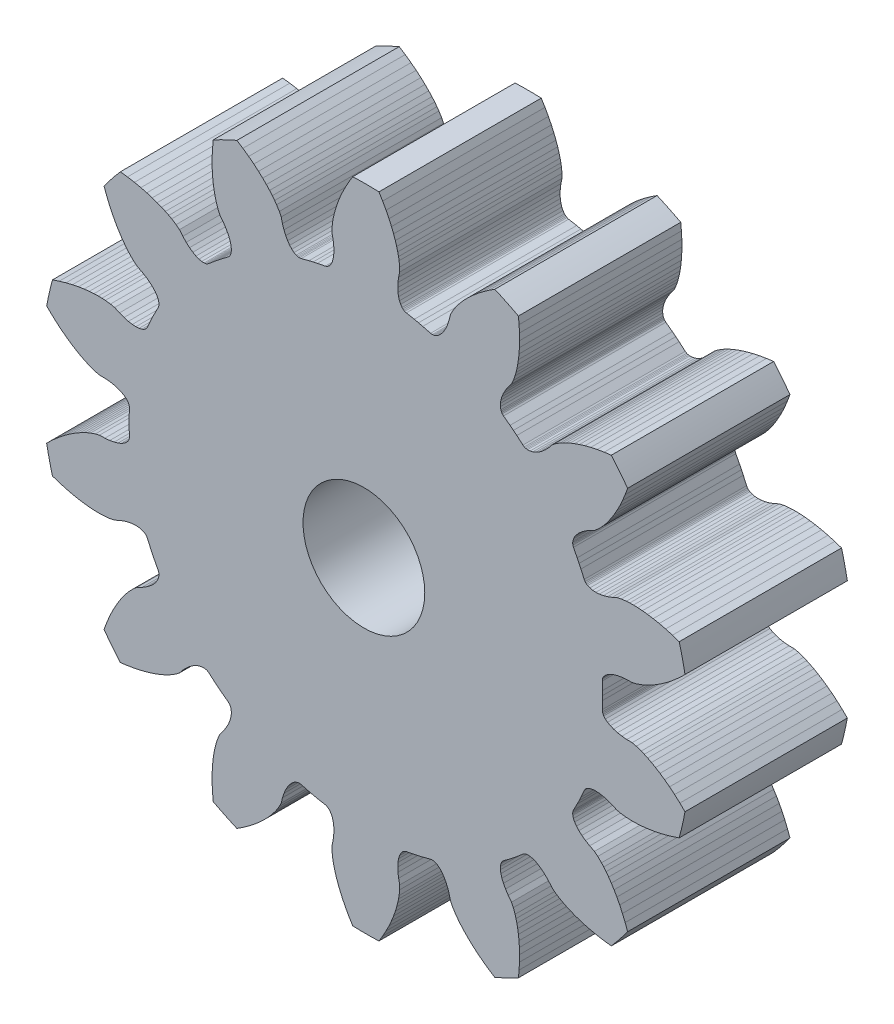
SolidWorks part; units mm, degrees
ref_plane "Front Plane" through (0, 0, 0) normal (0, 0, 1) x (1, 0, 0)
ref_plane "Top Plane" through (0, 0, 0) normal (0, 1, 0) x (1, 0, 0)
ref_plane "Right Plane" through (0, 0, 0) normal (1, 0, 0) x (0, 0, -1)
sketch "Model" plane through (0, 0, 0) normal (0, 0, 1) x (1, 0, 0)
  line L0 (0.9148, -6.8491) -> (1.0148, -6.6078)
  line L1 (1.0148, -6.6078) -> (1.1173, -6.3874)
  line L2 (1.1173, -6.3874) -> (1.2214, -6.1857)
  line L3 (1.2214, -6.1857) -> (1.3252, -6.004)
  line L4 (1.3252, -6.004) -> (1.4277, -5.8407)
  line L5 (1.4277, -5.8407) -> (1.5261, -5.6978)
  line L6 (1.5261, -5.6978) -> (1.6203, -5.5723)
  line L7 (1.6203, -5.5723) -> (1.708, -5.4652)
  line L8 (1.708, -5.4652) -> (1.7906, -5.3725)
  line L9 (1.7906, -5.3725) -> (1.9268, -5.2373)
  line L10 (1.9268, -5.2373) -> (2.0494, -5.137)
  line L11 (2.0494, -5.137) -> (2.2262, -5.0491)
  line L12 (2.2262, -5.0491) -> (2.3813, -4.9559)
  line L13 (2.3813, -4.9559) -> (2.5142, -4.8594)
  line L14 (2.5142, -4.8594) -> (2.6249, -4.7612)
  line L15 (2.6249, -4.7612) -> (2.7135, -4.663)
  line L16 (2.7135, -4.663) -> (2.7804, -4.5665)
  line L17 (2.7804, -4.5665) -> (2.8257, -4.4733)
  line L18 (2.8257, -4.4733) -> (2.8499, -4.385)
  line L19 (2.8499, -4.385) -> (2.8542, -4.3432)
  line L20 (2.8542, -4.3432) -> (2.8535, -4.3033)
  line L21 (2.8535, -4.3033) -> (2.8479, -4.2653)
  line L22 (2.8479, -4.2653) -> (2.8262, -4.2044)
  line L23 (2.8262, -4.2044) -> (2.6873, -3.9401)
  line L24 (2.6873, -3.9401) -> (2.6165, -3.7965)
  line L25 (2.6165, -3.7965) -> (2.5483, -3.6516)
  line L26 (2.5483, -3.6516) -> (2.4283, -3.3782)
  line L27 (2.4283, -3.3782) -> (2.3942, -3.3233)
  line L28 (2.3942, -3.3233) -> (2.3681, -3.2952)
  line L29 (2.3681, -3.2952) -> (2.3373, -3.2697)
  line L30 (2.3373, -3.2697) -> (2.3019, -3.2471)
  line L31 (2.3019, -3.2471) -> (2.2178, -3.211)
  line L32 (2.2178, -3.211) -> (2.1167, -3.1883)
  line L33 (2.1167, -3.1883) -> (1.9995, -3.1804)
  line L34 (1.9995, -3.1804) -> (1.8675, -3.1884)
  line L35 (1.8675, -3.1884) -> (1.7217, -3.2138)
  line L36 (1.7217, -3.2138) -> (1.5634, -3.2575)
  line L37 (1.5634, -3.2575) -> (1.3938, -3.3206)
  line L38 (1.3938, -3.3206) -> (1.2148, -3.4041)
  line L39 (1.2148, -3.4041) -> (1.06, -3.4374)
  line L40 (1.06, -3.4374) -> (0.8694, -3.4596)
  line L41 (0.8694, -3.4596) -> (0.7454, -3.4663)
  line L42 (0.7454, -3.4663) -> (0.607, -3.4681)
  line L43 (0.607, -3.4681) -> (0.4502, -3.4636)
  line L44 (0.4502, -3.4636) -> (0.2771, -3.4514)
  line L45 (0.2771, -3.4514) -> (0.0855, -3.4297)
  line L46 (0.0855, -3.4297) -> (-0.1213, -3.3975)
  line L47 (-0.1213, -3.3975) -> (-0.3439, -3.3532)
  line L48 (-0.3439, -3.3532) -> (-0.5801, -3.2959)
  line L49 (-0.5801, -3.2959) -> (-0.8311, -3.2237)
  line L50 (-0.8311, -3.2237) -> (-1.0818, -3.1401)
  line L51 (-1.2973, -2.1961) -> (-1.1076, -2.0119)
  line L52 (-1.1076, -2.0119) -> (-0.9129, -1.838)
  line L53 (-0.9129, -1.838) -> (-0.7249, -1.6838)
  line L54 (-0.7249, -1.6838) -> (-0.5436, -1.5473)
  line L55 (-0.5436, -1.5473) -> (-0.3713, -1.4286)
  line L56 (-0.3713, -1.4286) -> (-0.208, -1.326)
  line L57 (-0.208, -1.326) -> (-0.0574, -1.2399)
  line L58 (-0.0574, -1.2399) -> (0.0819, -1.1678)
  line L59 (0.0819, -1.1678) -> (0.2074, -1.1093)
  line L60 (0.2074, -1.1093) -> (0.3221, -1.0616)
  line L61 (0.3221, -1.0616) -> (0.5035, -0.9989)
  line L62 (0.5035, -0.9989) -> (0.6574, -0.9617)
  line L63 (0.6574, -0.9617) -> (0.8549, -0.9592)
  line L64 (0.8549, -0.9592) -> (1.035, -0.9426)
  line L65 (1.035, -0.9426) -> (1.1966, -0.9133)
  line L66 (1.1966, -0.9133) -> (1.339, -0.8728)
  line L67 (1.339, -0.8728) -> (1.4614, -0.8228)
  line L68 (1.4614, -0.8228) -> (1.5635, -0.7648)
  line L69 (1.5635, -0.7648) -> (1.6448, -0.7005)
  line L70 (1.6448, -0.7005) -> (1.7049, -0.6315)
  line L71 (1.7049, -0.6315) -> (1.727, -0.5957)
  line L72 (1.727, -0.5957) -> (1.7437, -0.5594)
  line L73 (1.7437, -0.5594) -> (1.755, -0.5228)
  line L74 (1.755, -0.5228) -> (1.7619, -0.4585)
  line L75 (1.7619, -0.4585) -> (1.7514, -0.1601)
  line L76 (1.7514, -0.1601) -> (1.75, 0)
  line L77 (1.75, 0) -> (1.7514, 0.1601)
  line L78 (1.7514, 0.1601) -> (1.7619, 0.4585)
  line L79 (1.7619, 0.4585) -> (1.755, 0.5228)
  line L80 (1.755, 0.5228) -> (1.7437, 0.5594)
  line L81 (1.7437, 0.5594) -> (1.727, 0.5957)
  line L82 (1.727, 0.5957) -> (1.7049, 0.6315)
  line L83 (1.7049, 0.6315) -> (1.6448, 0.7005)
  line L84 (1.6448, 0.7005) -> (1.5635, 0.7648)
  line L85 (1.5635, 0.7648) -> (1.4614, 0.8228)
  line L86 (1.4614, 0.8228) -> (1.339, 0.8728)
  line L87 (1.339, 0.8728) -> (1.1966, 0.9133)
  line L88 (1.1966, 0.9133) -> (1.035, 0.9426)
  line L89 (1.035, 0.9426) -> (0.8549, 0.9592)
  line L90 (0.8549, 0.9592) -> (0.6574, 0.9617)
  line L91 (0.6574, 0.9617) -> (0.5035, 0.9989)
  line L92 (0.5035, 0.9989) -> (0.3221, 1.0616)
  line L93 (0.3221, 1.0616) -> (0.2074, 1.1093)
  line L94 (0.2074, 1.1093) -> (0.0819, 1.1678)
  line L95 (0.0819, 1.1678) -> (-0.0574, 1.2399)
  line L96 (-0.0574, 1.2399) -> (-0.208, 1.326)
  line L97 (-0.208, 1.326) -> (-0.3713, 1.4286)
  line L98 (-0.3713, 1.4286) -> (-0.5436, 1.5473)
  line L99 (-0.5436, 1.5473) -> (-0.7249, 1.6838)
  line L100 (-0.7249, 1.6838) -> (-0.9129, 1.838)
  line L101 (-0.9129, 1.838) -> (-1.1076, 2.0119)
  line L102 (-1.1076, 2.0119) -> (-1.2973, 2.1961)
  line L103 (-1.0818, 3.1401) -> (-0.8311, 3.2237)
  line L104 (-0.8311, 3.2237) -> (-0.5801, 3.2959)
  line L105 (-0.5801, 3.2959) -> (-0.3439, 3.3532)
  line L106 (-0.3439, 3.3532) -> (-0.1213, 3.3975)
  line L107 (-0.1213, 3.3975) -> (0.0855, 3.4297)
  line L108 (0.0855, 3.4297) -> (0.2771, 3.4514)
  line L109 (0.2771, 3.4514) -> (0.4502, 3.4636)
  line L110 (0.4502, 3.4636) -> (0.607, 3.4681)
  line L111 (0.607, 3.4681) -> (0.7454, 3.4663)
  line L112 (0.7454, 3.4663) -> (0.8694, 3.4596)
  line L113 (0.8694, 3.4596) -> (1.06, 3.4374)
  line L114 (1.06, 3.4374) -> (1.2148, 3.4041)
  line L115 (1.2148, 3.4041) -> (1.3938, 3.3206)
  line L116 (1.3938, 3.3206) -> (1.5634, 3.2575)
  line L117 (1.5634, 3.2575) -> (1.7217, 3.2138)
  line L118 (1.7217, 3.2138) -> (1.8675, 3.1884)
  line L119 (1.8675, 3.1884) -> (1.9995, 3.1804)
  line L120 (1.9995, 3.1804) -> (2.1167, 3.1883)
  line L121 (2.1167, 3.1883) -> (2.2178, 3.211)
  line L122 (2.2178, 3.211) -> (2.3019, 3.2471)
  line L123 (2.3019, 3.2471) -> (2.3373, 3.2697)
  line L124 (2.3373, 3.2697) -> (2.3681, 3.2952)
  line L125 (2.3681, 3.2952) -> (2.3942, 3.3233)
  line L126 (2.3942, 3.3233) -> (2.4283, 3.3782)
  line L127 (2.4283, 3.3782) -> (2.5483, 3.6516)
  line L128 (2.5483, 3.6516) -> (2.6165, 3.7965)
  line L129 (2.6165, 3.7965) -> (2.6873, 3.9401)
  line L130 (2.6873, 3.9401) -> (2.8262, 4.2044)
  line L131 (2.8262, 4.2044) -> (2.8479, 4.2653)
  line L132 (2.8479, 4.2653) -> (2.8535, 4.3033)
  line L133 (2.8535, 4.3033) -> (2.8542, 4.3432)
  line L134 (2.8542, 4.3432) -> (2.8499, 4.385)
  line L135 (2.8499, 4.385) -> (2.8257, 4.4733)
  line L136 (2.8257, 4.4733) -> (2.7804, 4.5665)
  line L137 (2.7804, 4.5665) -> (2.7135, 4.663)
  line L138 (2.7135, 4.663) -> (2.6249, 4.7612)
  line L139 (2.6249, 4.7612) -> (2.5142, 4.8594)
  line L140 (2.5142, 4.8594) -> (2.3813, 4.9559)
  line L141 (2.3813, 4.9559) -> (2.2262, 5.0491)
  line L142 (2.2262, 5.0491) -> (2.0494, 5.137)
  line L143 (2.0494, 5.137) -> (1.9268, 5.2373)
  line L144 (1.9268, 5.2373) -> (1.7906, 5.3725)
  line L145 (1.7906, 5.3725) -> (1.708, 5.4652)
  line L146 (1.708, 5.4652) -> (1.6203, 5.5723)
  line L147 (1.6203, 5.5723) -> (1.5261, 5.6978)
  line L148 (1.5261, 5.6978) -> (1.4277, 5.8407)
  line L149 (1.4277, 5.8407) -> (1.3252, 6.004)
  line L150 (1.3252, 6.004) -> (1.2214, 6.1857)
  line L151 (1.2214, 6.1857) -> (1.1173, 6.3874)
  line L152 (1.1173, 6.3874) -> (1.0148, 6.6078)
  line L153 (1.0148, 6.6078) -> (0.9148, 6.8491)
  line L154 (0.9148, 6.8491) -> (0.8238, 7.0973)
  line L155 (1.4275, 7.8543) -> (1.6898, 7.8208)
  line L156 (1.6898, 7.8208) -> (1.9472, 7.777)
  line L157 (1.9472, 7.777) -> (2.1849, 7.7262)
  line L158 (2.1849, 7.7262) -> (2.4047, 7.6695)
  line L159 (2.4047, 7.6695) -> (2.6049, 7.6088)
  line L160 (2.6049, 7.6088) -> (2.7869, 7.5451)
  line L161 (2.7869, 7.5451) -> (2.9482, 7.4811)
  line L162 (2.9482, 7.4811) -> (3.0914, 7.4171)
  line L163 (3.0914, 7.4171) -> (3.2154, 7.3554)
  line L164 (3.2154, 7.3554) -> (3.3242, 7.2955)
  line L165 (3.3242, 7.2955) -> (3.4863, 7.1928)
  line L166 (3.4863, 7.1928) -> (3.6113, 7.0957)
  line L167 (3.6113, 7.0957) -> (3.7364, 6.9428)
  line L168 (3.7364, 6.9428) -> (3.8617, 6.8123)
  line L169 (3.8617, 6.8123) -> (3.9854, 6.7043)
  line L170 (3.9854, 6.7043) -> (4.1058, 6.6182)
  line L171 (4.1058, 6.6182) -> (4.2213, 6.5536)
  line L172 (4.2213, 6.5536) -> (4.3302, 6.51)
  line L173 (4.3302, 6.51) -> (4.4312, 6.4865)
  line L174 (4.4312, 6.4865) -> (4.5226, 6.4826)
  line L175 (4.5226, 6.4826) -> (4.5643, 6.4876)
  line L176 (4.5643, 6.4876) -> (4.6031, 6.4972)
  line L177 (4.6031, 6.4972) -> (4.6388, 6.5112)
  line L178 (4.6388, 6.5112) -> (4.6934, 6.5459)
  line L179 (4.6934, 6.5459) -> (4.9202, 6.7401)
  line L180 (4.9202, 6.7401) -> (5.0445, 6.841)
  line L181 (5.0445, 6.841) -> (5.1706, 6.9397)
  line L182 (5.1706, 6.9397) -> (5.4103, 7.1176)
  line L183 (5.4103, 7.1176) -> (5.4563, 7.1631)
  line L184 (5.4563, 7.1631) -> (5.4779, 7.1948)
  line L185 (5.4779, 7.1948) -> (5.4959, 7.2305)
  line L186 (5.4959, 7.2305) -> (5.5101, 7.27)
  line L187 (5.5101, 7.27) -> (5.5265, 7.3601)
  line L188 (5.5265, 7.3601) -> (5.5262, 7.4637)
  line L189 (5.5262, 7.4637) -> (5.5078, 7.5796)
  line L190 (5.5078, 7.5796) -> (5.4706, 7.7066)
  line L191 (5.4706, 7.7066) -> (5.4135, 7.8431)
  line L192 (5.4135, 7.8431) -> (5.3356, 7.9877)
  line L193 (5.3356, 7.9877) -> (5.2363, 8.1389)
  line L194 (5.2363, 8.1389) -> (5.1151, 8.2949)
  line L195 (5.1151, 8.2949) -> (5.0482, 8.4384)
  line L196 (5.0482, 8.4384) -> (4.9842, 8.6193)
  line L197 (4.9842, 8.6193) -> (4.95, 8.7387)
  line L198 (4.95, 8.7387) -> (4.9174, 8.8733)
  line L199 (4.9174, 8.8733) -> (4.8869, 9.0271)
  line L200 (4.8869, 9.0271) -> (4.8603, 9.1986)
  line L201 (4.8603, 9.1986) -> (4.8388, 9.3902)
  line L202 (4.8388, 9.3902) -> (4.8242, 9.599)
  line L203 (4.8242, 9.599) -> (4.8178, 9.8259)
  line L204 (4.8178, 9.8259) -> (4.8212, 10.0689)
  line L205 (4.8212, 10.0689) -> (4.8357, 10.3296)
  line L206 (4.8357, 10.3296) -> (4.8615, 10.5927)
  line L207 (5.7338, 11.0128) -> (5.9556, 10.8689)
  line L208 (5.9556, 10.8689) -> (6.1685, 10.7177)
  line L209 (6.1685, 10.7177) -> (6.3606, 10.5688)
  line L210 (6.3606, 10.5688) -> (6.534, 10.4224)
  line L211 (6.534, 10.4224) -> (6.6881, 10.2808)
  line L212 (6.6881, 10.2808) -> (6.8245, 10.1445)
  line L213 (6.8245, 10.1445) -> (6.942, 10.0168)
  line L214 (6.942, 10.0168) -> (7.0433, 9.897)
  line L215 (7.0433, 9.897) -> (7.1282, 9.7877)
  line L216 (7.1282, 9.7877) -> (7.2002, 9.6865)
  line L217 (7.2002, 9.6865) -> (7.3017, 9.5236)
  line L218 (7.3017, 9.5236) -> (7.3722, 9.3819)
  line L219 (7.3722, 9.3819) -> (7.4186, 9.1899)
  line L220 (7.4186, 9.1899) -> (7.4749, 9.0179)
  line L221 (7.4749, 9.0179) -> (7.5394, 8.8669)
  line L222 (7.5394, 8.8669) -> (7.6105, 8.7371)
  line L223 (7.6105, 8.7371) -> (7.6866, 8.6289)
  line L224 (7.6866, 8.6289) -> (7.7658, 8.5422)
  line L225 (7.7658, 8.5422) -> (7.8466, 8.4773)
  line L226 (7.8466, 8.4773) -> (7.9272, 8.4341)
  line L227 (7.9272, 8.4341) -> (7.967, 8.4205)
  line L228 (7.967, 8.4205) -> (8.0061, 8.4123)
  line L229 (8.0061, 8.4123) -> (8.0444, 8.4094)
  line L230 (8.0444, 8.4094) -> (8.1086, 8.417)
  line L231 (8.1086, 8.417) -> (8.3971, 8.4936)
  line L232 (8.3971, 8.4936) -> (8.5529, 8.5306)
  line L233 (8.5529, 8.5306) -> (8.7094, 8.5648)
  line L234 (8.7094, 8.5648) -> (9.0026, 8.621)
  line L235 (9.0026, 8.621) -> (9.0637, 8.6421)
  line L236 (9.0637, 8.6421) -> (9.0969, 8.6613)
  line L237 (9.0969, 8.6613) -> (9.1286, 8.6856)
  line L238 (9.1286, 8.6856) -> (9.1586, 8.7151)
  line L239 (9.1586, 8.7151) -> (9.2125, 8.7891)
  line L240 (9.2125, 8.7891) -> (9.2571, 8.8826)
  line L241 (9.2571, 8.8826) -> (9.2909, 8.995)
  line L242 (9.2909, 8.995) -> (9.3124, 9.1256)
  line L243 (9.3124, 9.1256) -> (9.3202, 9.2733)
  line L244 (9.3202, 9.2733) -> (9.3128, 9.4374)
  line L245 (9.3128, 9.4374) -> (9.2889, 9.6168)
  line L246 (9.2889, 9.6168) -> (9.2474, 9.8099)
  line L247 (9.2474, 9.8099) -> (9.2494, 9.9682)
  line L248 (9.2494, 9.9682) -> (9.2702, 10.159)
  line L249 (9.2702, 10.159) -> (9.2912, 10.2814)
  line L250 (9.2912, 10.2814) -> (9.3202, 10.4167)
  line L251 (9.3202, 10.4167) -> (9.3595, 10.5686)
  line L252 (9.3595, 10.5686) -> (9.41, 10.7346)
  line L253 (9.41, 10.7346) -> (9.4737, 10.9166)
  line L254 (9.4737, 10.9166) -> (9.5511, 11.111)
  line L255 (9.5511, 11.111) -> (9.6438, 11.3182)
  line L256 (9.6438, 11.3182) -> (9.7523, 11.5357)
  line L257 (9.7523, 11.5357) -> (9.8785, 11.7643)
  line L258 (9.8785, 11.7643) -> (10.0159, 11.9902)
  line L259 (10.9841, 11.9902) -> (11.1215, 11.7643)
  line L260 (11.1215, 11.7643) -> (11.2477, 11.5357)
  line L261 (11.2477, 11.5357) -> (11.3562, 11.3182)
  line L262 (11.3562, 11.3182) -> (11.4489, 11.111)
  line L263 (11.4489, 11.111) -> (11.5263, 10.9166)
  line L264 (11.5263, 10.9166) -> (11.59, 10.7346)
  line L265 (11.59, 10.7346) -> (11.6405, 10.5686)
  line L266 (11.6405, 10.5686) -> (11.6798, 10.4167)
  line L267 (11.6798, 10.4167) -> (11.7088, 10.2814)
  line L268 (11.7088, 10.2814) -> (11.7298, 10.159)
  line L269 (11.7298, 10.159) -> (11.7506, 9.9682)
  line L270 (11.7506, 9.9682) -> (11.7526, 9.8099)
  line L271 (11.7526, 9.8099) -> (11.7111, 9.6168)
  line L272 (11.7111, 9.6168) -> (11.6872, 9.4374)
  line L273 (11.6872, 9.4374) -> (11.6798, 9.2733)
  line L274 (11.6798, 9.2733) -> (11.6876, 9.1256)
  line L275 (11.6876, 9.1256) -> (11.7091, 8.995)
  line L276 (11.7091, 8.995) -> (11.7429, 8.8826)
  line L277 (11.7429, 8.8826) -> (11.7875, 8.7891)
  line L278 (11.7875, 8.7891) -> (11.8414, 8.7151)
  line L279 (11.8414, 8.7151) -> (11.8714, 8.6856)
  line L280 (11.8714, 8.6856) -> (11.9031, 8.6613)
  line L281 (11.9031, 8.6613) -> (11.9363, 8.6421)
  line L282 (11.9363, 8.6421) -> (11.9974, 8.621)
  line L283 (11.9974, 8.621) -> (12.2906, 8.5648)
  line L284 (12.2906, 8.5648) -> (12.4471, 8.5306)
  line L285 (12.4471, 8.5306) -> (12.6029, 8.4936)
  line L286 (12.6029, 8.4936) -> (12.8914, 8.417)
  line L287 (12.8914, 8.417) -> (12.9556, 8.4094)
  line L288 (12.9556, 8.4094) -> (12.9939, 8.4123)
  line L289 (12.9939, 8.4123) -> (13.033, 8.4205)
  line L290 (13.033, 8.4205) -> (13.0728, 8.4341)
  line L291 (13.0728, 8.4341) -> (13.1534, 8.4773)
  line L292 (13.1534, 8.4773) -> (13.2342, 8.5422)
  line L293 (13.2342, 8.5422) -> (13.3134, 8.6289)
  line L294 (13.3134, 8.6289) -> (13.3895, 8.7371)
  line L295 (13.3895, 8.7371) -> (13.4606, 8.8669)
  line L296 (13.4606, 8.8669) -> (13.5251, 9.0179)
  line L297 (13.5251, 9.0179) -> (13.5814, 9.1899)
  line L298 (13.5814, 9.1899) -> (13.6278, 9.3819)
  line L299 (13.6278, 9.3819) -> (13.6983, 9.5236)
  line L300 (13.6983, 9.5236) -> (13.7998, 9.6865)
  line L301 (13.7998, 9.6865) -> (13.8718, 9.7877)
  line L302 (13.8718, 9.7877) -> (13.9567, 9.897)
  line L303 (13.9567, 9.897) -> (14.058, 10.0168)
  line L304 (14.058, 10.0168) -> (14.1755, 10.1445)
  line L305 (14.1755, 10.1445) -> (14.3119, 10.2808)
  line L306 (14.3119, 10.2808) -> (14.466, 10.4224)
  line L307 (14.466, 10.4224) -> (14.6394, 10.5688)
  line L308 (14.6394, 10.5688) -> (14.8315, 10.7177)
  line L309 (14.8315, 10.7177) -> (15.0444, 10.8689)
  line L310 (15.0444, 10.8689) -> (15.2662, 11.0128)
  line L311 (16.1385, 10.5927) -> (16.1643, 10.3296)
  line L312 (16.1643, 10.3296) -> (16.1788, 10.0689)
  line L313 (16.1788, 10.0689) -> (16.1822, 9.8259)
  line L314 (16.1822, 9.8259) -> (16.1758, 9.599)
  line L315 (16.1758, 9.599) -> (16.1612, 9.3902)
  line L316 (16.1612, 9.3902) -> (16.1397, 9.1986)
  line L317 (16.1397, 9.1986) -> (16.1131, 9.0271)
  line L318 (16.1131, 9.0271) -> (16.0826, 8.8733)
  line L319 (16.0826, 8.8733) -> (16.05, 8.7387)
  line L320 (16.05, 8.7387) -> (16.0158, 8.6193)
  line L321 (16.0158, 8.6193) -> (15.9518, 8.4384)
  line L322 (15.9518, 8.4384) -> (15.8849, 8.2949)
  line L323 (15.8849, 8.2949) -> (15.7637, 8.1389)
  line L324 (15.7637, 8.1389) -> (15.6644, 7.9877)
  line L325 (15.6644, 7.9877) -> (15.5865, 7.8431)
  line L326 (15.5865, 7.8431) -> (15.5294, 7.7066)
  line L327 (15.5294, 7.7066) -> (15.4922, 7.5796)
  line L328 (15.4922, 7.5796) -> (15.4738, 7.4637)
  line L329 (15.4738, 7.4637) -> (15.4735, 7.3601)
  line L330 (15.4735, 7.3601) -> (15.4899, 7.27)
  line L331 (15.4899, 7.27) -> (15.5041, 7.2305)
  line L332 (15.5041, 7.2305) -> (15.5221, 7.1948)
  line L333 (15.5221, 7.1948) -> (15.5437, 7.1631)
  line L334 (15.5437, 7.1631) -> (15.5897, 7.1176)
  line L335 (15.5897, 7.1176) -> (15.8294, 6.9397)
  line L336 (15.8294, 6.9397) -> (15.9555, 6.841)
  line L337 (15.9555, 6.841) -> (16.0798, 6.7401)
  line L338 (16.0798, 6.7401) -> (16.3066, 6.5459)
  line L339 (16.3066, 6.5459) -> (16.3612, 6.5112)
  line L340 (16.3612, 6.5112) -> (16.3969, 6.4972)
  line L341 (16.3969, 6.4972) -> (16.4357, 6.4876)
  line L342 (16.4357, 6.4876) -> (16.4774, 6.4826)
  line L343 (16.4774, 6.4826) -> (16.5688, 6.4865)
  line L344 (16.5688, 6.4865) -> (16.6698, 6.51)
  line L345 (16.6698, 6.51) -> (16.7787, 6.5536)
  line L346 (16.7787, 6.5536) -> (16.8942, 6.6182)
  line L347 (16.8942, 6.6182) -> (17.0146, 6.7043)
  line L348 (17.0146, 6.7043) -> (17.1383, 6.8123)
  line L349 (17.1383, 6.8123) -> (17.2636, 6.9428)
  line L350 (17.2636, 6.9428) -> (17.3887, 7.0957)
  line L351 (17.3887, 7.0957) -> (17.5137, 7.1928)
  line L352 (17.5137, 7.1928) -> (17.6758, 7.2955)
  line L353 (17.6758, 7.2955) -> (17.7846, 7.3554)
  line L354 (17.7846, 7.3554) -> (17.9086, 7.4171)
  line L355 (17.9086, 7.4171) -> (18.0518, 7.4811)
  line L356 (18.0518, 7.4811) -> (18.2131, 7.5451)
  line L357 (18.2131, 7.5451) -> (18.3951, 7.6088)
  line L358 (18.3951, 7.6088) -> (18.5953, 7.6695)
  line L359 (18.5953, 7.6695) -> (18.8151, 7.7262)
  line L360 (18.8151, 7.7262) -> (19.0528, 7.777)
  line L361 (19.0528, 7.777) -> (19.3102, 7.8208)
  line L362 (19.3102, 7.8208) -> (19.5725, 7.8543)
  line L363 (20.1762, 7.0973) -> (20.0852, 6.8491)
  line L364 (20.0852, 6.8491) -> (19.9852, 6.6078)
  line L365 (19.9852, 6.6078) -> (19.8827, 6.3874)
  line L366 (19.8827, 6.3874) -> (19.7786, 6.1857)
  line L367 (19.7786, 6.1857) -> (19.6748, 6.004)
  line L368 (19.6748, 6.004) -> (19.5723, 5.8407)
  line L369 (19.5723, 5.8407) -> (19.4739, 5.6978)
  line L370 (19.4739, 5.6978) -> (19.3797, 5.5723)
  line L371 (19.3797, 5.5723) -> (19.292, 5.4652)
  line L372 (19.292, 5.4652) -> (19.2094, 5.3725)
  line L373 (19.2094, 5.3725) -> (19.0732, 5.2373)
  line L374 (19.0732, 5.2373) -> (18.9506, 5.137)
  line L375 (18.9506, 5.137) -> (18.7738, 5.0491)
  line L376 (18.7738, 5.0491) -> (18.6187, 4.9559)
  line L377 (18.6187, 4.9559) -> (18.4858, 4.8594)
  line L378 (18.4858, 4.8594) -> (18.3751, 4.7612)
  line L379 (18.3751, 4.7612) -> (18.2865, 4.663)
  line L380 (18.2865, 4.663) -> (18.2196, 4.5665)
  line L381 (18.2196, 4.5665) -> (18.1743, 4.4733)
  line L382 (18.1743, 4.4733) -> (18.1501, 4.385)
  line L383 (18.1501, 4.385) -> (18.1458, 4.3432)
  line L384 (18.1458, 4.3432) -> (18.1465, 4.3033)
  line L385 (18.1465, 4.3033) -> (18.1521, 4.2653)
  line L386 (18.1521, 4.2653) -> (18.1738, 4.2044)
  line L387 (18.1738, 4.2044) -> (18.3127, 3.9401)
  line L388 (18.3127, 3.9401) -> (18.3835, 3.7965)
  line L389 (18.3835, 3.7965) -> (18.4517, 3.6516)
  line L390 (18.4517, 3.6516) -> (18.5717, 3.3782)
  line L391 (18.5717, 3.3782) -> (18.6058, 3.3233)
  line L392 (18.6058, 3.3233) -> (18.6319, 3.2952)
  line L393 (18.6319, 3.2952) -> (18.6627, 3.2697)
  line L394 (18.6627, 3.2697) -> (18.6981, 3.2471)
  line L395 (18.6981, 3.2471) -> (18.7822, 3.211)
  line L396 (18.7822, 3.211) -> (18.8833, 3.1883)
  line L397 (18.8833, 3.1883) -> (19.0005, 3.1804)
  line L398 (19.0005, 3.1804) -> (19.1325, 3.1884)
  line L399 (19.1325, 3.1884) -> (19.2783, 3.2138)
  line L400 (19.2783, 3.2138) -> (19.4366, 3.2575)
  line L401 (19.4366, 3.2575) -> (19.6062, 3.3206)
  line L402 (19.6062, 3.3206) -> (19.7852, 3.4041)
  line L403 (19.7852, 3.4041) -> (19.94, 3.4374)
  line L404 (19.94, 3.4374) -> (20.1306, 3.4596)
  line L405 (20.1306, 3.4596) -> (20.2546, 3.4663)
  line L406 (20.2546, 3.4663) -> (20.393, 3.4681)
  line L407 (20.393, 3.4681) -> (20.5498, 3.4636)
  line L408 (20.5498, 3.4636) -> (20.7229, 3.4514)
  line L409 (20.7229, 3.4514) -> (20.9145, 3.4297)
  line L410 (20.9145, 3.4297) -> (21.1213, 3.3975)
  line L411 (21.1213, 3.3975) -> (21.3439, 3.3532)
  line L412 (21.3439, 3.3532) -> (21.5801, 3.2959)
  line L413 (21.5801, 3.2959) -> (21.8311, 3.2237)
  line L414 (21.8311, 3.2237) -> (22.0818, 3.1401)
  line L415 (22.2973, 2.1961) -> (22.1076, 2.0119)
  line L416 (22.1076, 2.0119) -> (21.9129, 1.838)
  line L417 (21.9129, 1.838) -> (21.7249, 1.6838)
  line L418 (21.7249, 1.6838) -> (21.5436, 1.5473)
  line L419 (21.5436, 1.5473) -> (21.3713, 1.4286)
  line L420 (21.3713, 1.4286) -> (21.208, 1.326)
  line L421 (21.208, 1.326) -> (21.0574, 1.2399)
  line L422 (21.0574, 1.2399) -> (20.9181, 1.1678)
  line L423 (20.9181, 1.1678) -> (20.7926, 1.1093)
  line L424 (20.7926, 1.1093) -> (20.6779, 1.0616)
  line L425 (20.6779, 1.0616) -> (20.4965, 0.9989)
  line L426 (20.4965, 0.9989) -> (20.3426, 0.9617)
  line L427 (20.3426, 0.9617) -> (20.1451, 0.9592)
  line L428 (20.1451, 0.9592) -> (19.965, 0.9426)
  line L429 (19.965, 0.9426) -> (19.8034, 0.9133)
  line L430 (19.8034, 0.9133) -> (19.661, 0.8728)
  line L431 (19.661, 0.8728) -> (19.5386, 0.8228)
  line L432 (19.5386, 0.8228) -> (19.4365, 0.7648)
  line L433 (19.4365, 0.7648) -> (19.3552, 0.7005)
  line L434 (19.3552, 0.7005) -> (19.2951, 0.6315)
  line L435 (19.2951, 0.6315) -> (19.273, 0.5957)
  line L436 (19.273, 0.5957) -> (19.2563, 0.5594)
  line L437 (19.2563, 0.5594) -> (19.245, 0.5228)
  line L438 (19.245, 0.5228) -> (19.2381, 0.4585)
  line L439 (19.2381, 0.4585) -> (19.2486, 0.1601)
  line L440 (19.2486, 0.1601) -> (19.25, 0)
  line L441 (19.25, 0) -> (19.2486, -0.1601)
  line L442 (19.2486, -0.1601) -> (19.2381, -0.4585)
  line L443 (19.2381, -0.4585) -> (19.245, -0.5228)
  line L444 (19.245, -0.5228) -> (19.2563, -0.5594)
  line L445 (19.2563, -0.5594) -> (19.273, -0.5957)
  line L446 (19.273, -0.5957) -> (19.2951, -0.6315)
  line L447 (19.2951, -0.6315) -> (19.3552, -0.7005)
  line L448 (19.3552, -0.7005) -> (19.4365, -0.7648)
  line L449 (19.4365, -0.7648) -> (19.5386, -0.8228)
  line L450 (19.5386, -0.8228) -> (19.661, -0.8728)
  line L451 (19.661, -0.8728) -> (19.8034, -0.9133)
  line L452 (19.8034, -0.9133) -> (19.965, -0.9426)
  line L453 (19.965, -0.9426) -> (20.1451, -0.9592)
  line L454 (20.1451, -0.9592) -> (20.3426, -0.9617)
  line L455 (20.3426, -0.9617) -> (20.4965, -0.9989)
  line L456 (20.4965, -0.9989) -> (20.6779, -1.0616)
  line L457 (20.6779, -1.0616) -> (20.7926, -1.1093)
  line L458 (20.7926, -1.1093) -> (20.9181, -1.1678)
  line L459 (20.9181, -1.1678) -> (21.0574, -1.2399)
  line L460 (21.0574, -1.2399) -> (21.208, -1.326)
  line L461 (21.208, -1.326) -> (21.3713, -1.4286)
  line L462 (21.3713, -1.4286) -> (21.5436, -1.5473)
  line L463 (21.5436, -1.5473) -> (21.7249, -1.6838)
  line L464 (21.7249, -1.6838) -> (21.9129, -1.838)
  line L465 (21.9129, -1.838) -> (22.1076, -2.0119)
  line L466 (22.1076, -2.0119) -> (22.2973, -2.1961)
  line L467 (22.0818, -3.1401) -> (21.8311, -3.2237)
  line L468 (21.8311, -3.2237) -> (21.5801, -3.2959)
  line L469 (21.5801, -3.2959) -> (21.3439, -3.3532)
  line L470 (21.3439, -3.3532) -> (21.1213, -3.3975)
  line L471 (21.1213, -3.3975) -> (20.9145, -3.4297)
  line L472 (20.9145, -3.4297) -> (20.7229, -3.4514)
  line L473 (20.7229, -3.4514) -> (20.5498, -3.4636)
  line L474 (20.5498, -3.4636) -> (20.393, -3.4681)
  line L475 (20.393, -3.4681) -> (20.2546, -3.4663)
  line L476 (20.2546, -3.4663) -> (20.1306, -3.4596)
  line L477 (20.1306, -3.4596) -> (19.94, -3.4374)
  line L478 (19.94, -3.4374) -> (19.7852, -3.4041)
  line L479 (19.7852, -3.4041) -> (19.6062, -3.3206)
  line L480 (19.6062, -3.3206) -> (19.4366, -3.2575)
  line L481 (19.4366, -3.2575) -> (19.2783, -3.2138)
  line L482 (19.2783, -3.2138) -> (19.1325, -3.1884)
  line L483 (19.1325, -3.1884) -> (19.0005, -3.1804)
  line L484 (19.0005, -3.1804) -> (18.8833, -3.1883)
  line L485 (18.8833, -3.1883) -> (18.7822, -3.211)
  line L486 (18.7822, -3.211) -> (18.6981, -3.2471)
  line L487 (18.6981, -3.2471) -> (18.6627, -3.2697)
  line L488 (18.6627, -3.2697) -> (18.6319, -3.2952)
  line L489 (18.6319, -3.2952) -> (18.6058, -3.3233)
  line L490 (18.6058, -3.3233) -> (18.5717, -3.3782)
  line L491 (18.5717, -3.3782) -> (18.4517, -3.6516)
  line L492 (18.4517, -3.6516) -> (18.3835, -3.7965)
  line L493 (18.3835, -3.7965) -> (18.3127, -3.9401)
  line L494 (18.3127, -3.9401) -> (18.1738, -4.2044)
  line L495 (18.1738, -4.2044) -> (18.1521, -4.2653)
  line L496 (18.1521, -4.2653) -> (18.1465, -4.3033)
  line L497 (18.1465, -4.3033) -> (18.1458, -4.3432)
  line L498 (18.1458, -4.3432) -> (18.1501, -4.385)
  line L499 (18.1501, -4.385) -> (18.1743, -4.4733)
  line L500 (18.1743, -4.4733) -> (18.2196, -4.5665)
  line L501 (18.2196, -4.5665) -> (18.2865, -4.663)
  line L502 (18.2865, -4.663) -> (18.3751, -4.7612)
  line L503 (18.3751, -4.7612) -> (18.4858, -4.8594)
  line L504 (18.4858, -4.8594) -> (18.6187, -4.9559)
  line L505 (18.6187, -4.9559) -> (18.7738, -5.0491)
  line L506 (18.7738, -5.0491) -> (18.9506, -5.137)
  line L507 (18.9506, -5.137) -> (19.0732, -5.2373)
  line L508 (19.0732, -5.2373) -> (19.2094, -5.3725)
  line L509 (19.2094, -5.3725) -> (19.292, -5.4652)
  line L510 (19.292, -5.4652) -> (19.3797, -5.5723)
  line L511 (19.3797, -5.5723) -> (19.4739, -5.6978)
  line L512 (19.4739, -5.6978) -> (19.5723, -5.8407)
  line L513 (19.5723, -5.8407) -> (19.6748, -6.004)
  line L514 (19.6748, -6.004) -> (19.7786, -6.1857)
  line L515 (19.7786, -6.1857) -> (19.8827, -6.3874)
  line L516 (19.8827, -6.3874) -> (19.9852, -6.6078)
  line L517 (19.9852, -6.6078) -> (20.0852, -6.8491)
  line L518 (20.0852, -6.8491) -> (20.1762, -7.0973)
  line L519 (19.5725, -7.8543) -> (19.3102, -7.8208)
  line L520 (19.3102, -7.8208) -> (19.0528, -7.777)
  line L521 (19.0528, -7.777) -> (18.8151, -7.7262)
  line L522 (18.8151, -7.7262) -> (18.5953, -7.6695)
  line L523 (18.5953, -7.6695) -> (18.3951, -7.6088)
  line L524 (18.3951, -7.6088) -> (18.2131, -7.5451)
  line L525 (18.2131, -7.5451) -> (18.0518, -7.4811)
  line L526 (18.0518, -7.4811) -> (17.9086, -7.4171)
  line L527 (17.9086, -7.4171) -> (17.7846, -7.3554)
  line L528 (17.7846, -7.3554) -> (17.6758, -7.2955)
  line L529 (17.6758, -7.2955) -> (17.5137, -7.1928)
  line L530 (17.5137, -7.1928) -> (17.3887, -7.0957)
  line L531 (17.3887, -7.0957) -> (17.2636, -6.9428)
  line L532 (17.2636, -6.9428) -> (17.1383, -6.8123)
  line L533 (17.1383, -6.8123) -> (17.0146, -6.7043)
  line L534 (17.0146, -6.7043) -> (16.8942, -6.6182)
  line L535 (16.8942, -6.6182) -> (16.7787, -6.5536)
  line L536 (16.7787, -6.5536) -> (16.6698, -6.51)
  line L537 (16.6698, -6.51) -> (16.5688, -6.4865)
  line L538 (16.5688, -6.4865) -> (16.4774, -6.4826)
  line L539 (16.4774, -6.4826) -> (16.4357, -6.4876)
  line L540 (16.4357, -6.4876) -> (16.3969, -6.4972)
  line L541 (16.3969, -6.4972) -> (16.3612, -6.5112)
  line L542 (16.3612, -6.5112) -> (16.3066, -6.5459)
  line L543 (16.3066, -6.5459) -> (16.0798, -6.7401)
  line L544 (16.0798, -6.7401) -> (15.9555, -6.841)
  line L545 (15.9555, -6.841) -> (15.8294, -6.9397)
  line L546 (15.8294, -6.9397) -> (15.5897, -7.1176)
  line L547 (15.5897, -7.1176) -> (15.5437, -7.1631)
  line L548 (15.5437, -7.1631) -> (15.5221, -7.1948)
  line L549 (15.5221, -7.1948) -> (15.5041, -7.2305)
  line L550 (15.5041, -7.2305) -> (15.4899, -7.27)
  line L551 (15.4899, -7.27) -> (15.4735, -7.3601)
  line L552 (15.4735, -7.3601) -> (15.4738, -7.4637)
  line L553 (15.4738, -7.4637) -> (15.4922, -7.5796)
  line L554 (15.4922, -7.5796) -> (15.5294, -7.7066)
  line L555 (15.5294, -7.7066) -> (15.5865, -7.8431)
  line L556 (15.5865, -7.8431) -> (15.6644, -7.9877)
  line L557 (15.6644, -7.9877) -> (15.7637, -8.1389)
  line L558 (15.7637, -8.1389) -> (15.8849, -8.2949)
  line L559 (15.8849, -8.2949) -> (15.9518, -8.4384)
  line L560 (15.9518, -8.4384) -> (16.0158, -8.6193)
  line L561 (16.0158, -8.6193) -> (16.05, -8.7387)
  line L562 (16.05, -8.7387) -> (16.0826, -8.8733)
  line L563 (16.0826, -8.8733) -> (16.1131, -9.0271)
  line L564 (16.1131, -9.0271) -> (16.1397, -9.1986)
  line L565 (16.1397, -9.1986) -> (16.1612, -9.3902)
  line L566 (16.1612, -9.3902) -> (16.1758, -9.599)
  line L567 (16.1758, -9.599) -> (16.1822, -9.8259)
  line L568 (16.1822, -9.8259) -> (16.1788, -10.0689)
  line L569 (16.1788, -10.0689) -> (16.1643, -10.3296)
  line L570 (16.1643, -10.3296) -> (16.1385, -10.5927)
  line L571 (15.2662, -11.0128) -> (15.0444, -10.8689)
  line L572 (15.0444, -10.8689) -> (14.8315, -10.7177)
  line L573 (14.8315, -10.7177) -> (14.6394, -10.5688)
  line L574 (14.6394, -10.5688) -> (14.466, -10.4224)
  line L575 (14.466, -10.4224) -> (14.3119, -10.2808)
  line L576 (14.3119, -10.2808) -> (14.1755, -10.1445)
  line L577 (14.1755, -10.1445) -> (14.058, -10.0168)
  line L578 (14.058, -10.0168) -> (13.9567, -9.897)
  line L579 (13.9567, -9.897) -> (13.8718, -9.7877)
  line L580 (13.8718, -9.7877) -> (13.7998, -9.6865)
  line L581 (13.7998, -9.6865) -> (13.6983, -9.5236)
  line L582 (13.6983, -9.5236) -> (13.6278, -9.3819)
  line L583 (13.6278, -9.3819) -> (13.5814, -9.1899)
  line L584 (13.5814, -9.1899) -> (13.5251, -9.0179)
  line L585 (13.5251, -9.0179) -> (13.4606, -8.8669)
  line L586 (13.4606, -8.8669) -> (13.3895, -8.7371)
  line L587 (13.3895, -8.7371) -> (13.3134, -8.6289)
  line L588 (13.3134, -8.6289) -> (13.2342, -8.5422)
  line L589 (13.2342, -8.5422) -> (13.1534, -8.4773)
  line L590 (13.1534, -8.4773) -> (13.0728, -8.4341)
  line L591 (13.0728, -8.4341) -> (13.033, -8.4205)
  line L592 (13.033, -8.4205) -> (12.9939, -8.4123)
  line L593 (12.9939, -8.4123) -> (12.9556, -8.4094)
  line L594 (12.9556, -8.4094) -> (12.8914, -8.417)
  line L595 (12.8914, -8.417) -> (12.6029, -8.4936)
  line L596 (12.6029, -8.4936) -> (12.4471, -8.5306)
  line L597 (12.4471, -8.5306) -> (12.2906, -8.5648)
  line L598 (12.2906, -8.5648) -> (11.9974, -8.621)
  line L599 (11.9974, -8.621) -> (11.9363, -8.6421)
  line L600 (11.9363, -8.6421) -> (11.9031, -8.6613)
  line L601 (11.9031, -8.6613) -> (11.8714, -8.6856)
  line L602 (11.8714, -8.6856) -> (11.8414, -8.7151)
  line L603 (11.8414, -8.7151) -> (11.7875, -8.7891)
  line L604 (11.7875, -8.7891) -> (11.7429, -8.8826)
  line L605 (11.7429, -8.8826) -> (11.7091, -8.995)
  line L606 (11.7091, -8.995) -> (11.6876, -9.1256)
  line L607 (11.6876, -9.1256) -> (11.6798, -9.2733)
  line L608 (11.6798, -9.2733) -> (11.6872, -9.4374)
  line L609 (11.6872, -9.4374) -> (11.7111, -9.6168)
  line L610 (11.7111, -9.6168) -> (11.7526, -9.8099)
  line L611 (11.7526, -9.8099) -> (11.7506, -9.9682)
  line L612 (11.7506, -9.9682) -> (11.7298, -10.159)
  line L613 (11.7298, -10.159) -> (11.7088, -10.2814)
  line L614 (11.7088, -10.2814) -> (11.6798, -10.4167)
  line L615 (11.6798, -10.4167) -> (11.6405, -10.5686)
  line L616 (11.6405, -10.5686) -> (11.59, -10.7346)
  line L617 (11.59, -10.7346) -> (11.5263, -10.9166)
  line L618 (11.5263, -10.9166) -> (11.4489, -11.111)
  line L619 (11.4489, -11.111) -> (11.3562, -11.3182)
  line L620 (11.3562, -11.3182) -> (11.2477, -11.5357)
  line L621 (11.2477, -11.5357) -> (11.1215, -11.7643)
  line L622 (11.1215, -11.7643) -> (10.9841, -11.9902)
  line L623 (10.0159, -11.9902) -> (9.8785, -11.7643)
  line L624 (9.8785, -11.7643) -> (9.7523, -11.5357)
  line L625 (9.7523, -11.5357) -> (9.6438, -11.3182)
  line L626 (9.6438, -11.3182) -> (9.5511, -11.111)
  line L627 (9.5511, -11.111) -> (9.4737, -10.9166)
  line L628 (9.4737, -10.9166) -> (9.41, -10.7346)
  line L629 (9.41, -10.7346) -> (9.3595, -10.5686)
  line L630 (9.3595, -10.5686) -> (9.3202, -10.4167)
  line L631 (9.3202, -10.4167) -> (9.2912, -10.2814)
  line L632 (9.2912, -10.2814) -> (9.2702, -10.159)
  line L633 (9.2702, -10.159) -> (9.2494, -9.9682)
  line L634 (9.2494, -9.9682) -> (9.2474, -9.8099)
  line L635 (9.2474, -9.8099) -> (9.2889, -9.6168)
  line L636 (9.2889, -9.6168) -> (9.3128, -9.4374)
  line L637 (9.3128, -9.4374) -> (9.3202, -9.2733)
  line L638 (9.3202, -9.2733) -> (9.3124, -9.1256)
  line L639 (9.3124, -9.1256) -> (9.2909, -8.995)
  line L640 (9.2909, -8.995) -> (9.2571, -8.8826)
  line L641 (9.2571, -8.8826) -> (9.2125, -8.7891)
  line L642 (9.2125, -8.7891) -> (9.1586, -8.7151)
  line L643 (9.1586, -8.7151) -> (9.1286, -8.6856)
  line L644 (9.1286, -8.6856) -> (9.0969, -8.6613)
  line L645 (9.0969, -8.6613) -> (9.0637, -8.6421)
  line L646 (9.0637, -8.6421) -> (9.0026, -8.621)
  line L647 (9.0026, -8.621) -> (8.7094, -8.5648)
  line L648 (8.7094, -8.5648) -> (8.5529, -8.5306)
  line L649 (8.5529, -8.5306) -> (8.3971, -8.4936)
  line L650 (8.3971, -8.4936) -> (8.1086, -8.417)
  line L651 (8.1086, -8.417) -> (8.0444, -8.4094)
  line L652 (8.0444, -8.4094) -> (8.0061, -8.4123)
  line L653 (8.0061, -8.4123) -> (7.967, -8.4205)
  line L654 (7.967, -8.4205) -> (7.9272, -8.4341)
  line L655 (7.9272, -8.4341) -> (7.8466, -8.4773)
  line L656 (7.8466, -8.4773) -> (7.7658, -8.5422)
  line L657 (7.7658, -8.5422) -> (7.6866, -8.6289)
  line L658 (7.6866, -8.6289) -> (7.6105, -8.7371)
  line L659 (7.6105, -8.7371) -> (7.5394, -8.8669)
  line L660 (7.5394, -8.8669) -> (7.4749, -9.0179)
  line L661 (7.4749, -9.0179) -> (7.4186, -9.1899)
  line L662 (7.4186, -9.1899) -> (7.3722, -9.3819)
  line L663 (7.3722, -9.3819) -> (7.3017, -9.5236)
  line L664 (7.3017, -9.5236) -> (7.2002, -9.6865)
  line L665 (7.2002, -9.6865) -> (7.1282, -9.7877)
  line L666 (7.1282, -9.7877) -> (7.0433, -9.897)
  line L667 (7.0433, -9.897) -> (6.942, -10.0168)
  line L668 (6.942, -10.0168) -> (6.8245, -10.1445)
  line L669 (6.8245, -10.1445) -> (6.6881, -10.2808)
  line L670 (6.6881, -10.2808) -> (6.534, -10.4224)
  line L671 (6.534, -10.4224) -> (6.3606, -10.5688)
  line L672 (6.3606, -10.5688) -> (6.1685, -10.7177)
  line L673 (6.1685, -10.7177) -> (5.9556, -10.8689)
  line L674 (5.9556, -10.8689) -> (5.7338, -11.0128)
  line L675 (4.8615, -10.5927) -> (4.8357, -10.3296)
  line L676 (4.8357, -10.3296) -> (4.8212, -10.0689)
  line L677 (4.8212, -10.0689) -> (4.8178, -9.8259)
  line L678 (4.8178, -9.8259) -> (4.8242, -9.599)
  line L679 (4.8242, -9.599) -> (4.8388, -9.3902)
  line L680 (4.8388, -9.3902) -> (4.8603, -9.1986)
  line L681 (4.8603, -9.1986) -> (4.8869, -9.0271)
  line L682 (4.8869, -9.0271) -> (4.9174, -8.8733)
  line L683 (4.9174, -8.8733) -> (4.95, -8.7387)
  line L684 (4.95, -8.7387) -> (4.9842, -8.6193)
  line L685 (4.9842, -8.6193) -> (5.0482, -8.4384)
  line L686 (5.0482, -8.4384) -> (5.1151, -8.2949)
  line L687 (5.1151, -8.2949) -> (5.2363, -8.1389)
  line L688 (5.2363, -8.1389) -> (5.3356, -7.9877)
  line L689 (5.3356, -7.9877) -> (5.4135, -7.8431)
  line L690 (5.4135, -7.8431) -> (5.4706, -7.7066)
  line L691 (5.4706, -7.7066) -> (5.5078, -7.5796)
  line L692 (5.5078, -7.5796) -> (5.5262, -7.4637)
  line L693 (5.5262, -7.4637) -> (5.5265, -7.3601)
  line L694 (5.5265, -7.3601) -> (5.5101, -7.27)
  line L695 (5.5101, -7.27) -> (5.4959, -7.2305)
  line L696 (5.4959, -7.2305) -> (5.4779, -7.1948)
  line L697 (5.4779, -7.1948) -> (5.4563, -7.1631)
  line L698 (5.4563, -7.1631) -> (5.4103, -7.1176)
  line L699 (5.4103, -7.1176) -> (5.1706, -6.9397)
  line L700 (5.1706, -6.9397) -> (5.0445, -6.841)
  line L701 (5.0445, -6.841) -> (4.9202, -6.7401)
  line L702 (4.9202, -6.7401) -> (4.6934, -6.5459)
  line L703 (4.6934, -6.5459) -> (4.6388, -6.5112)
  line L704 (4.6388, -6.5112) -> (4.6031, -6.4972)
  line L705 (4.6031, -6.4972) -> (4.5643, -6.4876)
  line L706 (4.5643, -6.4876) -> (4.5226, -6.4826)
  line L707 (4.5226, -6.4826) -> (4.4312, -6.4865)
  line L708 (4.4312, -6.4865) -> (4.3302, -6.51)
  line L709 (4.3302, -6.51) -> (4.2213, -6.5536)
  line L710 (4.2213, -6.5536) -> (4.1058, -6.6182)
  line L711 (4.1058, -6.6182) -> (3.9854, -6.7043)
  line L712 (3.9854, -6.7043) -> (3.8617, -6.8123)
  line L713 (3.8617, -6.8123) -> (3.7364, -6.9428)
  line L714 (3.7364, -6.9428) -> (3.6113, -7.0957)
  line L715 (3.6113, -7.0957) -> (3.4863, -7.1928)
  line L716 (3.4863, -7.1928) -> (3.3242, -7.2955)
  line L717 (3.3242, -7.2955) -> (3.2154, -7.3554)
  line L718 (3.2154, -7.3554) -> (3.0914, -7.4171)
  line L719 (3.0914, -7.4171) -> (2.9482, -7.4811)
  line L720 (2.9482, -7.4811) -> (2.7869, -7.5451)
  line L721 (2.7869, -7.5451) -> (2.6049, -7.6088)
  line L722 (2.6049, -7.6088) -> (2.4047, -7.6695)
  line L723 (2.4047, -7.6695) -> (2.1849, -7.7262)
  line L724 (2.1849, -7.7262) -> (1.9472, -7.777)
  line L725 (1.9472, -7.777) -> (1.6898, -7.8208)
  line L726 (1.6898, -7.8208) -> (1.4275, -7.8543)
  line L727 (0.8238, -7.0973) -> (0.9148, -6.8491)
  arc A0 (-1.2973, -2.1961) -> (-1.0818, -3.1401) centre (10.5, 0) ccw
  arc A1 (-1.0818, 3.1401) -> (-1.2973, 2.1961) centre (10.5, 0) ccw
  arc A2 (1.4275, 7.8543) -> (0.8238, 7.0973) centre (10.5, 0) ccw
  arc A3 (5.7338, 11.0128) -> (4.8615, 10.5927) centre (10.5, 0) ccw
  arc A4 (10.9841, 11.9902) -> (10.0159, 11.9902) centre (10.5, 0) ccw
  arc A5 (16.1385, 10.5927) -> (15.2662, 11.0128) centre (10.5, 0) ccw
  arc A6 (20.1762, 7.0973) -> (19.5725, 7.8543) centre (10.5, 0) ccw
  arc A7 (22.2973, 2.1961) -> (22.0818, 3.1401) centre (10.5, 0) ccw
  arc A8 (22.0818, -3.1401) -> (22.2973, -2.1961) centre (10.5, 0) ccw
  arc A9 (19.5725, -7.8543) -> (20.1762, -7.0973) centre (10.5, 0) ccw
  arc A10 (15.2662, -11.0128) -> (16.1385, -10.5927) centre (10.5, 0) ccw
  arc A11 (10.0159, -11.9902) -> (10.9841, -11.9902) centre (10.5, 0) ccw
  arc A12 (4.8615, -10.5927) -> (5.7338, -11.0128) centre (10.5, 0) ccw
  arc A13 (0.8238, -7.0973) -> (1.4275, -7.8543) centre (10.5, 0) ccw
extrude "Boss-Extrude1" add sketch "Model" along normal blind 6
sketch "Sketch2" plane through (0, 0, 6) normal (0, 0, 1) x (1, 0, 0)
  circle A0 centre (10.4281, 0) radius 2.25
  circle A1 centre (10.4281, 0) radius 12.5762 construction
  arc A2 (10.0159, -11.9902) -> (10.9841, -11.9902) centre (10.5, 0) ccw construction
  dimension "D1" = 4.5
  dimension "D2" = 0
  dimension "D3" = 10.4281
  dimension "D4" = 0.0719
extrude "Cut-Extrude1" cut sketch "Sketch2" against normal blind 10
